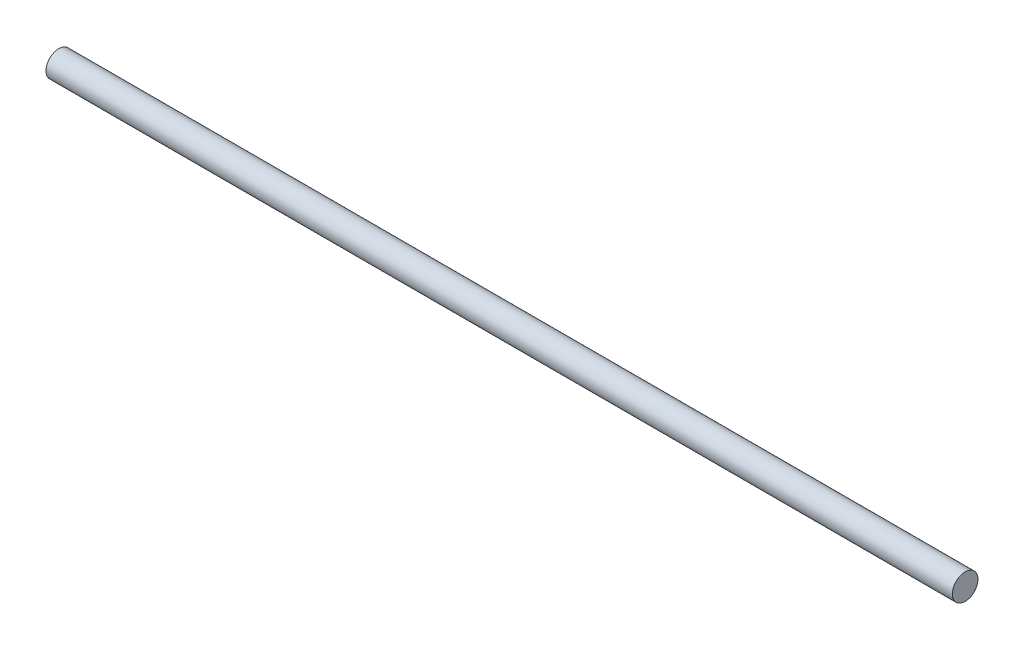
SolidWorks part; units mm, degrees
ref_plane "Top Plane" through (0, 0, 0) normal (0, 0, 1) x (1, 0, 0)
ref_plane "Right Plane" through (0, 0, 0) normal (0, 1, 0) x (1, 0, 0)
ref_plane "Front Plane" through (0, 0, 0) normal (1, 0, 0) x (0, 0, -1)
sketch "Sketch2" plane through (0, 0, 0) normal (1, 0, 0) x (0, 0, -1)
  circle A0 centre (0, 0) radius 1.5
  dimension "D1" = 3
extrude "Boss-Extrude1" add sketch "Sketch2" along normal blind 106
